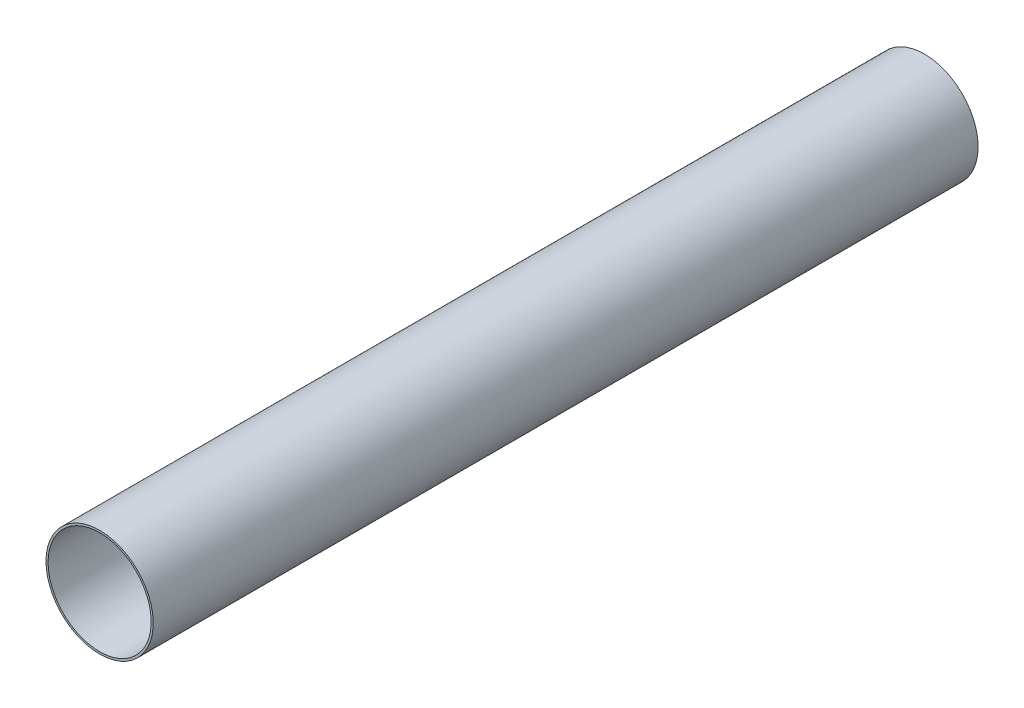
SolidWorks part; units mm, degrees
ref_plane "Front Plane" through (0, 0, 0) normal (0, 0, 1) x (1, 0, 0)
ref_plane "Top Plane" through (0, 0, 0) normal (0, 1, 0) x (1, 0, 0)
ref_plane "Right Plane" through (0, 0, 0) normal (1, 0, 0) x (0, 0, -1)
sketch "Sketch1" plane through (0, 0, 0) normal (0, 0, 1) x (1, 0, 0)
  circle A0 centre (0, 0) radius 38.1
  circle A1 centre (0, 0) radius 39.624
  dimension "D1" = 76.2
  dimension "D2" = 79.248
extrude "Boss-Extrude1" add sketch "Sketch1" along normal blind 609.6
